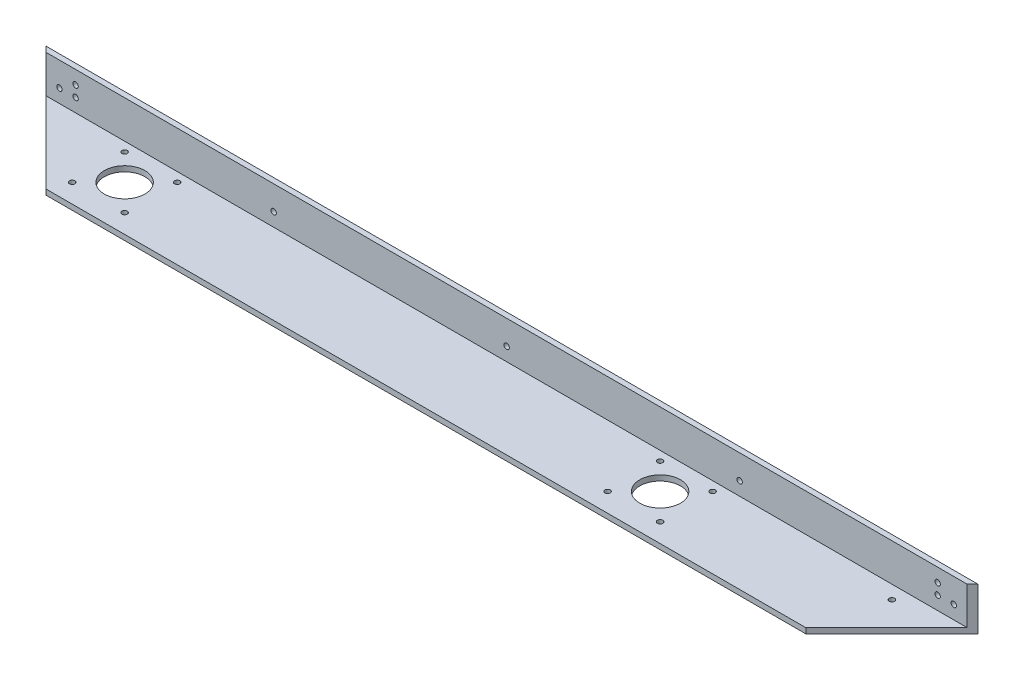
SolidWorks part; units mm, degrees
ref_plane "Front Plane" through (0, 0, 0) normal (0, 0, 1) x (1, 0, 0)
ref_plane "Top Plane" through (0, 0, 0) normal (0, 1, 0) x (1, 0, 0)
ref_plane "Right Plane" through (0, 0, 0) normal (1, 0, 0) x (0, 0, -1)
sketch "Sketch1" plane through (0, 0, 0) normal (1, 0, 0) x (0, 0, -1)
  line L0 (0, 0) -> (-50.8, 0)
  line L1 (-50.8, 0) -> (-50.8, 3.175)
  line L2 (-50.8, 3.175) -> (-3.175, 3.175)
  line L3 (-3.175, 3.175) -> (-3.175, 25.4)
  line L4 (-3.175, 25.4) -> (0, 25.4)
  line L5 (0, 25.4) -> (0, 0)
  dimension "LHeight" = 25.4
  dimension "LWidth" = 50.8
  dimension "LMaterialThickness" = 3.175
  dimension "D1" = 47.625
  dimension "D2" = 22.225
  dimension "D3" = 3.175
extrude "Boss-Extrude1" add sketch "Sketch1" along normal blind 550
chamfer "Chamfer7" distance 50.8 angle 45 1 edges at (0, 1.5875, 50.8)
chamfer "Chamfer8" distance 50.8 angle 45 1 edges at (550, 1.5875, 50.8)
sketch "BotthomHoles-Sketch2" plane through (0, 3.175, 0) normal (0, 1, 0) x (1, 0, 0)
  line L0 (546.825, -3.175) -> (3.175, -3.175) construction
  circle A0 centre (70.575, -24.175) radius 12
  circle A1 centre (386.575, -24.175) radius 12
  circle A2 centre (55.075, -8.675) radius 1.5875
  circle A3 centre (86.075, -8.675) radius 1.5875
  circle A4 centre (371.075, -8.675) radius 1.5875
  circle A5 centre (402.075, -8.675) radius 1.5875
  circle A6 centre (55.075, -39.675) radius 1.5875
  circle A7 centre (86.075, -39.675) radius 1.5875
  circle A8 centre (371.075, -39.675) radius 1.5875
  circle A9 centre (402.075, -39.675) radius 1.5875
  circle A11 centre (510.3125, -11.1125) radius 1.5875
  dimension "D9" = 3.175
  dimension "D10" = 24
  dimension "D2" = 8.675
  dimension "D3" = 31
  dimension "D4" = 15.5
  dimension "D5" = 15.5
  dimension "D6" = 31
  dimension "D7" = 15.5
  dimension "D8" = 31
  dimension "D11" = 21
  dimension "D12" = 316
  dimension "D13" = 70.575
  dimension "D17" = 39.6875
extrude "BottomHoles-Cut-Extrude1" cut sketch "BotthomHoles-Sketch2" against normal through all
sketch "LeftSideHoles-Sketch3" plane through (0, 0, 0) normal (0, 0, -1) x (-1, 0, 0)
  line L0 (0, 0) -> (0, 25.4) construction
  line L1 (-550, 0) -> (-550, 25.4) construction
  line L2 (-550, 25.4) -> (0, 25.4) construction
  circle A1 centre (-529.3625, 17.4625) radius 1.5875
  circle A2 centre (-538.8875, 11.1125) radius 1.5875
  circle A3 centre (-529.3625, 11.1125) radius 1.5875
  circle A4 centre (-11.1125, 11.1125) radius 1.5875
  circle A5 centre (-20.6375, 11.1125) radius 1.5875
  circle A6 centre (-20.6375, 17.4625) radius 1.5875
  circle A8 centre (-412.5, 11.1125) radius 1.5875
  circle A9 centre (-275, 11.1125) radius 1.5875
  circle A10 centre (-137.5, 11.1125) radius 1.5875
  dimension "D7" = 3.175
  dimension "D2" = 20.6375
  dimension "D4" = 11.1125
  dimension "D6" = 20.6375
  dimension "D8" = 137.5
  dimension "D9" = 137.5
  dimension "D10" = 137.5
  dimension "D5" = 11.1125
  dimension "D11" = 11.1125
  dimension "D3" = 7.9375
extrude "LeftSideHoles-Cut-Extrude2" cut sketch "LeftSideHoles-Sketch3" against normal through all
equation "\"LowerRailWidth\"= 2.00in"
equation "\"LowerRailHeight\"= 1.00in"
equation "\"RailThickness\"= .125in'Spec"
equation "\"SideRailHoleY1FromEdge\"= \"HoleOffsetFromEdge\""
equation "\"SideRailHoleX1FromSide\"= \"HoleOffsetFromSide\""
equation "\"StepperHoleDiameter\"= 24mm"
equation "\"StepperMountingHoleDiameter\"= 3.175mm"
equation "\"SideRailLength\"= 550mm"
equation "\"StepperMountingHoleDistance\"= 31mm'Spec"
equation "\"VSWidth\"= 1.25in'Spec"
equation "\"StepperMountingHoleOffsetFromLeftOrRightSide\"= \"StepperMountingHoleOffsetFromItsSide\" + \"RailThickness\""
equation "\"HoleOffsetFromEdge\"= \"RailThickness\" * 2.5"
equation "\"HoleOffsetFromSide\"= \"RailThickness\" * 3.5"
equation "\"StepperMountingHoleOffsetFromItsSide\"= 5.5mm'Spec"
equation "\"SideRailHoleX2FromSide\"= \"VSWidth\" - \"HoleOffsetFromEdge\" - \"RailThickness\"'Equals 20.6375"
equation "\"FasteningHoleDiameter\"= .125in"
equation "\"SideRailHoleY2FromSide\"= \"HoleOffsetFromSide\""
equation "\"LHeight@Sketch1\"=\"LowerRailHeight\""
equation "\"LWidth@Sketch1\"=\"LowerRailWidth\""
equation "\"D1@Chamfer7\"=\"LowerRailWidth\""
equation "\"D1@Chamfer8\"=\"LowerRailWidth\""
equation "\"D2@BotthomHoles-Sketch2\" = \"StepperMountingHoleOffsetFromLeftOrRightSide\""
equation "\"D3@BotthomHoles-Sketch2\" = \"StepperMountingHoleDistance\""
equation "\"D4@BotthomHoles-Sketch2\" = \"StepperMountingHoleDistance\" / 2"
equation "\"D5@BotthomHoles-Sketch2\"= \"StepperMountingHoleDistance\" / 2"
equation "\"D6@BotthomHoles-Sketch2\" = \"StepperMountingHoleDistance\""
equation "\"D7@BotthomHoles-Sketch2\" = \"StepperMountingHoleDistance\" / 2"
equation "\"D8@BotthomHoles-Sketch2\" = \"StepperMountingHoleDistance\""
equation "\"D9@BotthomHoles-Sketch2\" = \"StepperMountingHoleDiameter\""
equation "\"D10@BotthomHoles-Sketch2\" = \"StepperHoleDiameter\""
equation "\"D2@LeftSideHoles-Sketch3\" = \"SideRailHoleX2FromSide\""
equation "\"D4@LeftSideHoles-Sketch3\" = \"SideRailHoleY2FromSide\""
equation "\"D7@LeftSideHoles-Sketch3\" = \"FasteningHoleDiameter\""
equation "\"D1@Boss-Extrude1\"=\"SideRailLength\""
equation "\"D6@LeftSideHoles-Sketch3\"=\"SideRailHoleX2FromSide\""
equation "\"DistanceBetweenFrontToBackStepperHoles\"= \"BedLength\" - \"DistanceFromBedFrontToFirstLeftStepperHole\"'Equals 316"
equation "\"BedOverlap\"= 20mm"
equation "\"BedThirdSize\"= 70mm"
equation "\"BedLWidth\"= \"BedThirdSize\" + \"BedOverlap\"'Equals 90"
equation "\"BedInnerSquareWidth\"= \"BedThirdSize\" * 3'Equals 210"
equation "\"BedInnerSquareLength\"= \"BedInnerSquareWidth\""
equation "\"BedLength\"= \"BedInnerSquareLength\" + \"BedLWidth\" * 2 - \"BedOverlap\" * 2 + \"BedIncreasedByLength\"'Equals 350"
equation "\"D12@BotthomHoles-Sketch2\"=\"DistanceBetweenFrontToBackStepperHoles\""
equation "\"DistanceFromFrontSideToFirstLeftStepperHole\"= \"DistanceFromFrontSideToBedFront\" + \"DistanceFromBedFrontToFirstLeftStepperHole\"'Equals 70.575"
equation "\"D13@BotthomHoles-Sketch2\"=\"DistanceFromFrontSideToFirstLeftStepperHole\""
equation "\"DistanceFromBedFrontToFirstLeftStepperHole\"= \"LeadScrewNutPadSize\" + 10mm'Equals 34"
equation "\"DistanceFromFrontSideToBedFront\"= \"RailThickness\" + \"BeltTensionerDepth\" + 10mm'Equals 36.575"
equation "\"BeltTensionerDepth\"= \"BeltTensionerBackWallThickness\" + \"BeltTensionerInnerDepth\"'Equals 23.4"
equation "\"BeltTensionerBackWallThickness\"= 4mm"
equation "\"20TGT2PulleyDiameter\"= 17.9mm'Spec"
equation "\"BeltTensionerSpaceBetweenPulleyAndWall\"= 1.5mm"
equation "\"BeltTensionerInnerDepth\"= \"20TGT2PulleyDiameter\" + \"BeltTensionerSpaceBetweenPulleyAndWall\""
equation "\"BedIncreasedByLength\"= 0mm"
equation "\"LowerCornerBlockWidth\"= \"LowerRailWidth\" - \"RailThickness\" * 2'Room for left front stepper"
equation "\"D17@BotthomHoles-Sketch2\"=\"CornerEnclosureOffset\""
equation "\"LowerCornerBlockY1FromSide\"= \"HoleOffsetFromSide\""
equation "\"CornerEnclosureOffset\"= \"LowerCornerBlockWidth\" - \"HoleOffsetFromEdge\" + \"RailThickness\""
equation "\"LeadScrewNutMountingHoleFlangeDiameter\"= 22mm'Spec"
equation "\"LeadScrewNutPadSize\"= \"LeadScrewNutMountingHoleFlangeDiameter\" + 2mm'Equals 24"
equation "\"LeftOrRightEnclosureOffsets\"= \"SideRailLength\" / 4"
equation "\"D8@LeftSideHoles-Sketch3\"=\"LeftOrRightEnclosureOffsets\""
equation "\"D9@LeftSideHoles-Sketch3\"=\"LeftOrRightEnclosureOffsets\""
equation "\"D10@LeftSideHoles-Sketch3\"=\"LeftOrRightEnclosureOffsets\""
equation "\"D5@LeftSideHoles-Sketch3\"=\"SideRailHoleX1FromSide\""
equation "\"D11@LeftSideHoles-Sketch3\"=\"SideRailHoleX1FromSide\""
equation "\"D3@LeftSideHoles-Sketch3\"=\"SideRailHoleY1FromEdge\""
